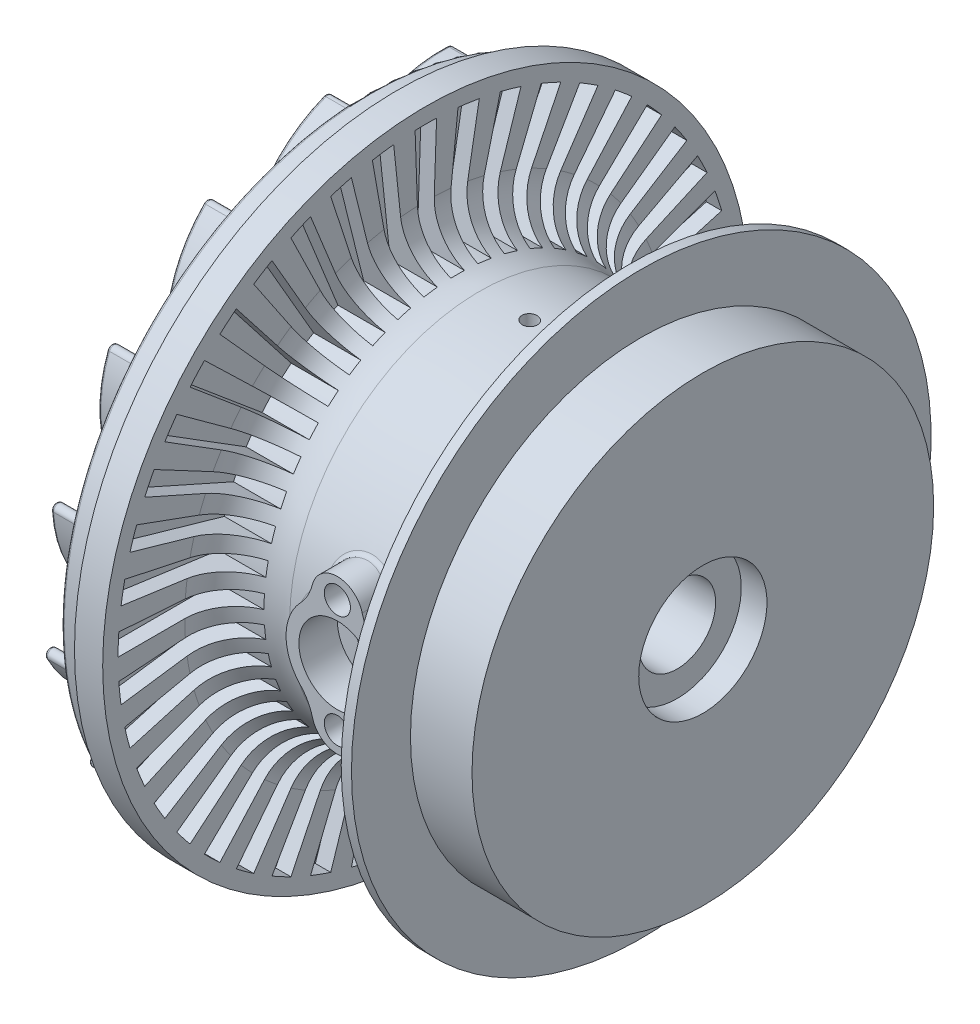
SolidWorks part; units mm, degrees
material "Plain Carbon Steel"
ref_plane "Front Plane" through (0, 0, 0) normal (0, 0, 1) x (1, 0, 0)
ref_plane "Top Plane" through (0, 0, 0) normal (0, 1, 0) x (1, 0, 0)
ref_plane "Right Plane" through (0, 0, 0) normal (1, 0, 0) x (0, 0, -1)
sketch "Sketch1" plane through (0, 0, 0) normal (0, 0, 1) x (1, 0, 0)
  line L0 (-31.25, 0) -> (31.25, 0) construction
  line L1 (-31.25, 0) -> (-31.25, 42) construction
  line L2 (-31.25, 42) -> (-33.75, 42)
  line L3 (-33.75, 42) -> (-33.75, 60)
  line L4 (-33.75, 60) -> (-28.25, 60)
  line L5 (-28.25, 60) -> (-28.25, 63)
  line L6 (-28.25, 63) -> (-22.75, 63)
  line L7 (-22.75, 63) -> (-22.75, 47)
  line L8 (31.25, 0) -> (31.25, 45) construction
  line L9 (31.25, 45) -> (19.25, 45)
  line L10 (19.25, 45) -> (19.25, 56.5)
  line L11 (19.25, 56.5) -> (17.25, 56.5)
  line L12 (17.25, 56.5) -> (17.25, 40.5)
  line L13 (-31.25, 7.5) -> (26.25, 7.5)
  line L14 (26.25, 7.5) -> (26.25, 12.5)
  line L15 (26.25, 12.5) -> (31.25, 12.5)
  line L16 (-31.25, 42) -> (-31.25, 7.5)
  line L17 (31.25, 45) -> (31.25, 12.5)
  arc A0 (-22.75, 47) -> (-12.2767, 37.0112) centre (-12.75, 47) ccw
  arc A1 (-12.2767, 37.0112) -> (11.41, 35.5711) centre (-7.07, -72.8655) cw
  arc A2 (11.41, 35.5711) -> (17.25, 40.5) centre (12.25, 40.5) ccw
  dimension "D12" = 10
  dimension "D13" = 110
  dimension "D14" = 5
  dimension "D15" = 5
  dimension "D1" = 62.5
  dimension "D2" = 42
  dimension "D3" = 2.5
  dimension "D4" = 18
  dimension "D5" = 5.5
  dimension "D6" = 3
  dimension "D7" = 45
  dimension "D8" = 12
  dimension "D9" = 11.5
  dimension "D10" = 2
  dimension "D11" = 16
  dimension "D16" = 7.5
  dimension "D17" = 12.5
revolve "Revolve1" add sketch "Sketch1" angle 360 about L0
sketch "Sketch2" plane through (-22.75, 0, 0) normal (1, 0, 0) x (0, 0, -1)
  line L0 (0, 0) -> (0, 60) construction
  line L1 (0, 0) -> (2.094, 59.9634) construction
  line L2 (0, 0) -> (-2.094, 59.9634) construction
  line L3 (-2.094, 59.9634) -> (-1.3175, 37.727)
  line L4 (2.094, 59.9634) -> (1.3175, 37.727)
  circle A0 centre (0, 0) radius 37.75 construction
  circle A1 centre (0, 0) radius 60 construction
  arc A2 (-2.094, 59.9634) -> (2.094, 59.9634) centre (0, 0) cw
  arc A3 (-1.3175, 37.727) -> (1.3175, 37.727) centre (0, 0) cw
  dimension "D1" = 75.5
  dimension "D2" = 120
  dimension "D3" = 2
extrude "Cut-Extrude1" cut sketch "Sketch2" against normal blind 3 and the other way blind 20
pattern_circular "CirPattern1" count 45 over 360 about axis through (-22.75, 0, 0) along (-1, 0, 0) of "Cut-Extrude1"
fillet "Fillet1" radius 0.5 2 edges at (-33.75, 0, 42) (-33.75, 0, 60)
sketch "Sketch4" plane through (-33.75, 0, 0) normal (-1, 0, 0) x (0, 0, 1)
  line L0 (0, 0) -> (0, 44.5) construction
  line L1 (0, 44.5) -> (-20.5284, 53.7107) construction
  arc A0 (-20.5284, 53.7107) -> (0, 44.5) centre (-19.4035, 28.736) cw construction
  arc A1 (0.7761, 45.1306) -> (-20.5734, 54.7097) centre (-19.4035, 28.736) ccw
  circle A2 centre (0, 0) radius 44.5
  circle A3 centre (0, 0) radius 44.5 construction
  arc A4 (-0.7761, 43.8694) -> (-20.4834, 52.7117) centre (-19.4035, 28.736) ccw
  circle A5 centre (0, 0) radius 57.5
  circle A6 centre (0, 0) radius 57.5 construction
  arc A7 (-0.7761, 43.8694) -> (0.7761, 45.1306) centre (0, 44.5) ccw
  arc A8 (-20.5734, 54.7097) -> (-20.4834, 52.7117) centre (-20.5284, 53.7107) ccw
  point P3 (-9.1694, 51.5453)
  dimension "D3" = 22.5
  dimension "D4" = 1
  dimension "D5" = 25
  dimension "D1" = 2
  dimension "D2" = 2
extrude "Boss-Extrude1" add sketch "Sketch4" along normal blind 5.5
fillet "Fillet2" radius 0.5 8 edges at (-33.75, 53.6657, -21.5273) (-33.75, 52.4577, -8.7601) (-33.75, 43.7239, 0.6306) (-39.25, 50.6329, -9.5788) (-39.25, 53.6657, -21.5273) (-39.25, 52.4577, -8.7601) (-39.25, 43.7239, 0.6306) (-33.75, 50.6329, -9.5788)
pattern_circular "CirPattern2" count 15 over 360 about axis through (-31.25, 0, 0) along (-1, 0, 0) of "Boss-Extrude1", "Fillet2" reverse direction yes
sketch "Sketch5" plane through (0, 0, 0) normal (0, 0, 1) x (1, 0, 0)
  line L0 (26.25, 0) -> (-31.25, 0) construction
  line L1 (-31.25, 7.5) -> (-31.25, -7.5) construction
  line L2 (26.25, -12.5) -> (26.25, 12.5) construction
  line L3 (-12.5, 15.5) -> (12.5, 15.5)
  line L4 (0, 0) -> (0, 15.5) construction
  line L5 (12.5, 15.5) -> (12.5, 0)
  line L6 (-12.5, 15.5) -> (-12.5, 8.5)
  dimension "D1" = 15.5
  dimension "D2" = 25
  dimension "D3" = 7
sweep "Cut-Sweep1" cut path "Sketch5" circular profile diameter 3 parameters "D3"=3
sketch "Sketch12" plane through (0, 0, 0) normal (0, 0, 1) x (1, 0, 0)
  line L0 (-15.25, -13.5) -> (15.25, -13.5)
  line L1 (0, -13.5) -> (0, 0) construction
  line L2 (15.25, -13.5) -> (15.25, 0)
  line L3 (-15.25, -13.5) -> (-15.25, 0)
  point P7 (0, 0)
  dimension "D1" = 13.5
  dimension "D2" = 30.5
sweep "Cut-Sweep2" cut path "Sketch12" circular profile diameter 3 parameters "D3"=3
sketch "Sketch19" plane through (0, 0, 0) normal (0, 1, 0) x (1, 0, 0)
  circle A0 centre (0, 0) radius 1.5
  dimension "D1" = 3
extrude "Cut-Extrude2" cut sketch "Sketch19" against normal through all from vertex starting at point (0, -13.5, 0)
sketch "Sketch20" plane through (0, 0, 0) normal (0, 1, 0) x (1, 0, 0)
  line L0 (26.25, 0) -> (-31.25, 0) construction
  circle A0 centre (-2.5, 0) radius 1.5
  dimension "D2" = 3
  dimension "D1" = 2.5
extrude "Cut-Extrude3" cut sketch "Sketch20" along normal through all from vertex starting at point (-12.5, 15.5, 0)
sketch "Sketch21" plane through (0, 0, 0) normal (0, 0, 1) x (1, 0, 0)
  arc A0 (-7.2618, 6.875) -> (-7.2618, -6.875) centre (0, 0) ccw
  arc A1 (4.8412, 11.25) -> (-4.8412, 11.25) centre (0, 10) ccw
  arc A2 (-4.8412, -11.25) -> (4.8412, -11.25) centre (0, -10) ccw
  arc A3 (7.2618, -6.875) -> (7.2618, 6.875) centre (0, 0) ccw
  arc A4 (-4.8412, -11.25) -> (-7.2618, -6.875) centre (-14.5237, -13.75) ccw
  arc A5 (-4.8412, 11.25) -> (-7.2618, 6.875) centre (-14.5237, 13.75) cw
  arc A6 (4.8412, -11.25) -> (7.2618, -6.875) centre (14.5237, -13.75) cw
  arc A7 (4.8412, 11.25) -> (7.2618, 6.875) centre (14.5237, 13.75) ccw
  point P14 (4.8412, -8.75)
  dimension "D1" = 20
  dimension "D2" = 10
  dimension "D3" = 10
  dimension "D4" = 10
extrude "Boss-Extrude2" add sketch "Sketch21" against normal up to next from offset 40
fillet "Fillet3" radius 1 8 edges at (-5.4272, -9.5961, 35.8605) (-9.9624, 0.8659, 37.0864) (-6.1484, 8.286, 36.1943) (-0.1922, 14.9963, 33.7364) (5.4955, 9.4498, 35.1669) (9.9653, -0.8321, 35.7977) (6.0605, -8.4232, 35.3585) (0.4316, -14.9813, 33.6983)
sketch "Sketch22" plane through (0, 0, 40) normal (0, 0, 1) x (1, 0, 0)
  circle A0 centre (0, 0) radius 3.75
  circle A1 centre (0, 0) radius 7.5
  dimension "D1" = 7.5
  dimension "D2" = 15
extrude "Cut-Extrude4" cut sketch "Sketch22" against normal blind 7.5
extrude "Cut-Extrude5" cut sketch "Sketch22<3>" against normal up to next contours A0 region at (0, 0, 40)
sketch "Sketch22<3>" plane through (0, 0, 40) normal (0, 0, 1) x (1, 0, 0) same geometry as "Sketch22"
sketch "Sketch23" plane through (0, 0, 40) normal (0, 0, 1) x (1, 0, 0)
  line L0 (0, 11) -> (0, -11) construction
  dimension "D1" = 22
sketch "Sketch26" plane through (0, 0, 40) normal (0, 0, 1) x (1, 0, 0)
  point P0 (0, 11)
  point P3 (0, -11)
hole_wizard "Ø5.1 (5.1) Diameter Hole1" positions "Sketch26" profile "Sketch27" hole size "Ø5.1" standard "ISO"
sketch "Sketch27" plane through (0, 11, 40) normal (1, 0, 0) x (0, -1, 0)
  line L0 (0, 0) -> (0, 12.6891)
  line L1 (0, 12.6891) -> (2.55, 11.5)
  line L2 (2.55, 11.5) -> (2.55, 0)
  line L5 (2.55, 0) -> (0, 0)
  line L10 (0, 12.6891) -> (-2.55, 11.5) construction
  line L11 (0, -6.35) -> (0, 107.95) construction
  dimension "Hole Dia." = 5.1
  dimension "Hole Depth" = 11.5
  dimension "Drill Angle" = 130
